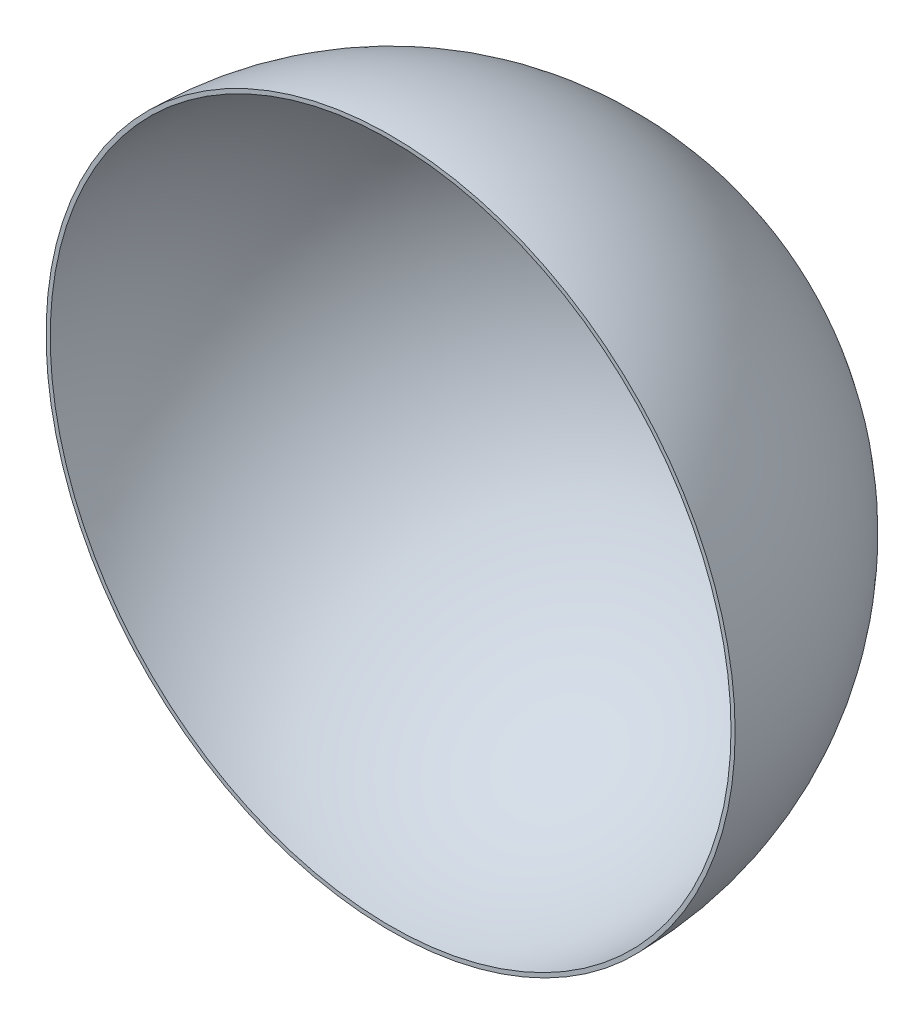
SolidWorks part; units mm, degrees
ref_plane "Ebene vorne" through (0, 0, 0) normal (0, 0, 1) x (1, 0, 0)
ref_plane "Ebene oben" through (0, 0, 0) normal (0, 1, 0) x (1, 0, 0)
ref_plane "Ebene rechts" through (0, 0, 0) normal (1, 0, 0) x (0, 0, -1)
sketch "Skizze1" plane through (0, 0, 0) normal (0, 0, 1) x (1, 0, 0)
  arc A0 (-250, 0) -> (250, 0) centre (0, 0) ccw
  dimension "D1" = 250
ref_axis "Achse1" through (-250, 0, 0) along (1, 0, 0)
revolve "Rotation-Dünn1" add sketch "Skizze1" angle 180 about axis through (-250, 0, 0) along (1, 0, 0) wall 3
ref_plane "Ebene2" through (0, 0, 0) normal (0, 0, 1) x (1, 0, 0)
ref_axis "Achse2" through (0, 0, 0) along (0, 0, 1)
